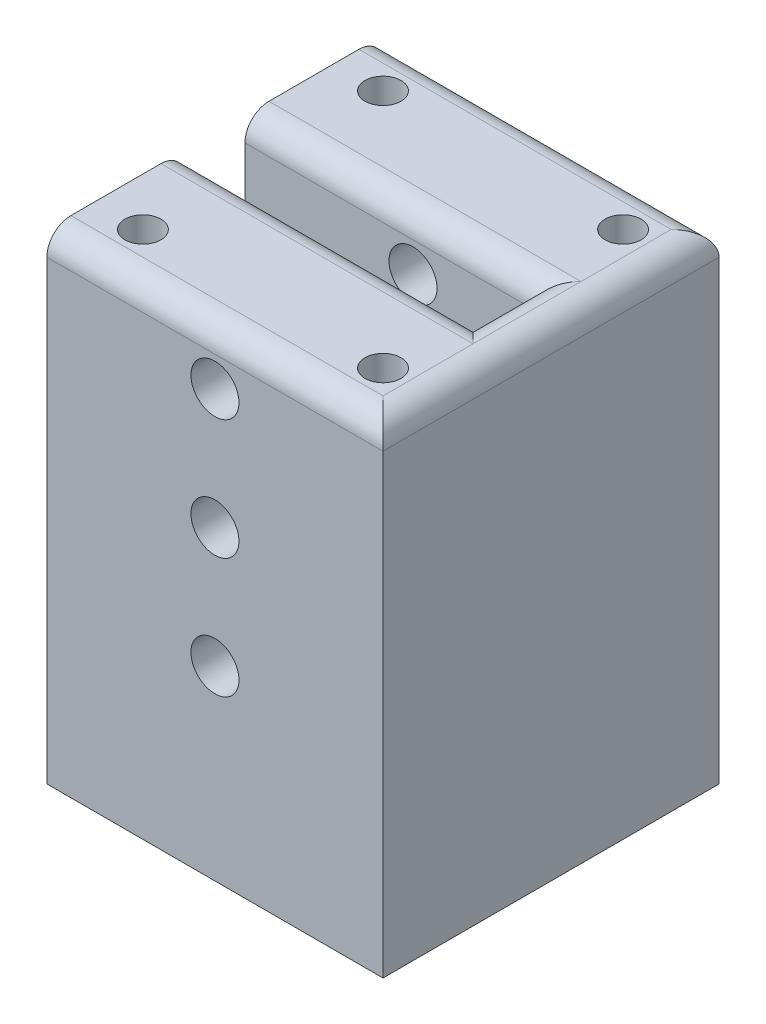
SolidWorks part; units mm, degrees
ref_plane "Ebene vorne" through (0, 0, 0) normal (0, 0, 1) x (1, 0, 0)
ref_plane "Ebene oben" through (0, 0, 0) normal (0, 1, 0) x (1, 0, 0)
ref_plane "Ebene rechts" through (0, 0, 0) normal (1, 0, 0) x (0, 0, -1)
sketch "Skizze2" plane through (0, 0, 0) normal (0, 1, 0) x (1, 0, 0)
  line L0 (-20.2432, 9.9977) -> (-0.2432, 9.9977) construction
  line L1 (-0.2432, 9.9977) -> (-0.2432, -10.0023) construction
  line L2 (-0.2432, -10.0023) -> (-20.2432, -10.0023) construction
  line L3 (-20.2432, -10.0023) -> (-20.2432, 9.9977) construction
  line L5 (-24.2432, 13.9977) -> (3.7568, 13.9977)
  line L6 (-24.2432, 13.9977) -> (-24.2432, -14.0023)
  line L7 (-24.2432, -14.0023) -> (3.7568, -14.0023)
  line L8 (3.7568, 13.9977) -> (3.7568, -14.0023)
  circle A0 centre (-20.2432, 9.9977) radius 1.5
  circle A1 centre (-0.2432, 9.9977) radius 1.5
  circle A2 centre (-20.2432, -10.0023) radius 1.5
  circle A3 centre (-0.2432, -10.0023) radius 1.5
  dimension "D1" = 3
  dimension "D2" = 3
  dimension "D3" = 3
  dimension "D4" = 3
  dimension "D5" = 20
  dimension "D6" = 20
  dimension "D7" = 4
  dimension "D8" = 4
  dimension "D9" = 4
  dimension "D10" = 4
extrude "Aufsatz-Linear austragen1" add sketch "Skizze2" along normal blind 40
sketch "Skizze3" plane through (0, 40, 0) normal (0, 1, 0) x (1, 0, 0)
  line L0 (-24.2432, 13.9977) -> (-24.2432, -14.0023) construction
  line L1 (-24.2432, 2.4977) -> (-0.2432, 2.4977)
  line L2 (-24.2432, 2.4977) -> (-24.2432, -2.5023)
  line L3 (-24.2432, -2.5023) -> (-0.2432, -2.5023)
  line L4 (-0.2432, 2.4977) -> (-0.2432, -2.5023)
  line L6 (-24.2432, -0.0023) -> (-0.2432, -0.0023) construction
  line L8 (3.7568, 13.9977) -> (-24.2432, 13.9977) construction
  line L9 (3.7568, -14.0023) -> (3.7568, 13.9977) construction
  dimension "D1" = 5
  dimension "D2" = 14
  dimension "D3" = 4
extrude "Schnitt-Linear austragen1" cut sketch "Skizze3" against normal blind 30
hole_wizard "Ø4.0 (4) Durchmesser Bohrung1" positions "Skizze4" profile "Skizze5" hole size "Ø4.0" standard "DIN" end condition through all
sketch "Skizze4" plane through (0, 0, 14.0023) normal (0, 0, 1) x (1, 0, 0)
  line L0 (-10.2432, 40) -> (-10.2432, 0) construction
  line L1 (-24.2432, 40) -> (3.7568, 40) construction
  line L2 (-24.2432, 0) -> (3.7568, 0) construction
  point P9 (-10.2432, 35.5)
  point P11 (-10.2432, 25.5)
  point P13 (-10.2432, 15.5)
  dimension "D1" = 4.5
  dimension "D2" = 10
  dimension "D3" = 10
sketch "Skizze5" plane through (-10.2432, 15.5, 14.0023) normal (1, 0, 0) x (0, -1, 0)
  line L0 (0, 0) -> (0, 28)
  line L1 (0, 28) -> (2, 28)
  line L2 (2, 28) -> (2, 0)
  line L5 (2, 0) -> (0, 0)
  line L11 (0, -6.35) -> (0, 107.95) construction
  dimension "Bohrerdurchmesser" = 4
  dimension "Bohrungstiefe" = 28
fillet "Verrundung1" radius 2 6 edges at (-0.2432, 40, 0.0023) (-12.2432, 40, 2.5023) (-12.2432, 40, -2.4977) (-10.2432, 40, -13.9977) (3.7568, 40, 0.0023) (-10.2432, 40, 14.0023)
